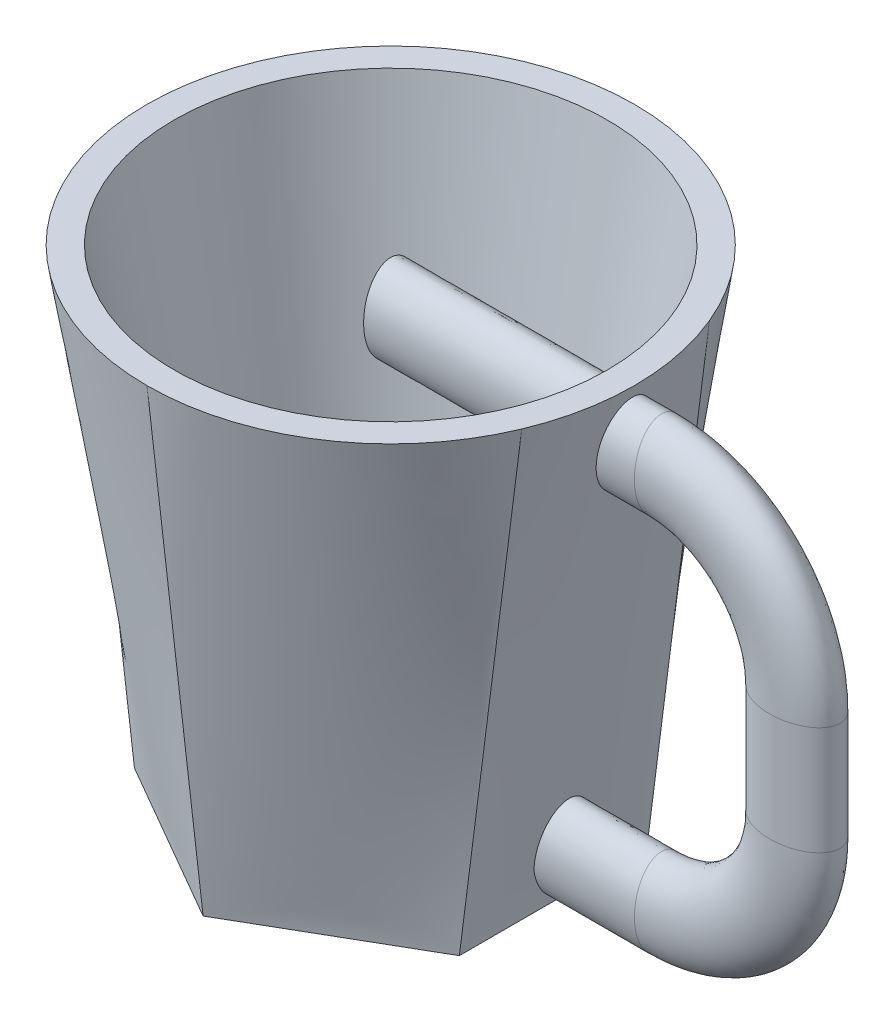
SolidWorks part; units mm, degrees
ref_plane "Front Plane" through (0, 0, 0) normal (0, 0, 1) x (1, 0, 0)
ref_plane "Top Plane" through (0, 0, 0) normal (0, 1, 0) x (1, 0, 0)
ref_plane "Right Plane" through (0, 0, 0) normal (1, 0, 0) x (0, 0, -1)
sketch "Sketch1" plane through (0, 0, 0) normal (0, 1, 0) x (1, 0, 0)
  line L0 (30, 17.3205) -> (0, 34.641)
  line L1 (0, 34.641) -> (-30, 17.3205)
  line L2 (-30, 17.3205) -> (-30, -17.3205)
  line L3 (-30, -17.3205) -> (0, -34.641)
  line L4 (0, -34.641) -> (30, -17.3205)
  line L5 (30, -17.3205) -> (30, 17.3205)
  circle A0 centre (0, 0) radius 30 construction
  dimension "D1" = 60
ref_plane "Plane1" through (0, 90, 0) normal (0, 1, 0) x (1, 0, 0)
sketch "Sketch2" plane through (0, 90, 0) normal (0, 1, 0) x (1, 0, 0)
  arc A0 (-41.5298, 17.3285) -> (-41.5298, -17.3285) centre (0, 0) ccw
  arc A1 (0, 45) -> (-41.5298, 17.3285) centre (0, 0) ccw
  arc A2 (41.5298, 17.3285) -> (0, 45) centre (0, 0) ccw
  arc A3 (41.5298, -17.3285) -> (41.5298, 17.3285) centre (0, 0) ccw
  arc A4 (0, -45) -> (41.5298, -17.3285) centre (0, 0) ccw
  arc A5 (-41.5298, -17.3285) -> (0, -45) centre (0, 0) ccw
  point P3 (0, 0)
  point P10 (0, 0)
  point P14 (-40.3577, 20.6366)
  point P15 (-38.9816, 22.4819)
  point P16 (0, 0)
  point P17 (0, 0)
  point P18 (0, 0)
  point P19 (0, 0)
  point P20 (-41.5298, 17.3205)
  dimension "D1" = 90
loft "Loft4" add profiles "Sketch1", "Sketch2" connector at (-30, 0, -17.3205) connector at (-41.5298, 90, -17.3285)
sketch "Sketch3" plane through (0, 0, 0) normal (0, 0, 1) x (1, 0, 0)
  line L0 (-40, 90) -> (-29.7979, 32.1411)
  line L1 (49.5076, 90) -> (-49.5076, 90) construction
  line L2 (0, 0) -> (0, 90) construction
  line L3 (-30, 0) -> (0, 0) construction
  line L4 (0, 5) -> (0, 109.9812) construction
  line L5 (0, 5) -> (0, 90)
  line L6 (0, 90) -> (-40, 90)
  arc A0 (-29.7979, 32.1411) -> (0, 5) centre (2.6773, 37.8674) ccw
  dimension "D1" = 5
  dimension "D2" = 10
  dimension "D3" = 40
revolve "Cut-Revolve1" cut sketch "Sketch3" angle 360 mid plane about L4
sketch "Sketch4" plane through (0, 0, 0) normal (0, 0, 1) x (1, 0, 0)
  line L0 (0, 80) -> (50, 80)
  line L1 (75, 55) -> (75, 35)
  line L2 (50, 10) -> (31.2811, 10)
  line L3 (30, 0) -> (41.5298, 90) construction
  line L4 (0, 0) -> (30, 0) construction
  line L5 (0, 0) -> (0, 90) construction
  arc A0 (50, 80) -> (75, 55) centre (50, 55) cw
  arc A1 (75, 35) -> (50, 10) centre (50, 35) cw
  point P13 (0, 0)
  point P14 (0, 80)
  point P17 (31.2811, 10)
  point P18 (31.2811, 10)
  point P19 (0, 0)
  dimension "D3" = 25
  dimension "D4" = 25
  dimension "D1" = 70
  dimension "D2" = 10
  dimension "D5" = 105
sketch "Sketch5" plane through (0, 0, 0) normal (1, 0, 0) x (0, 0, -1)
  line L0 (0, 80) -> (0, 55) construction
  ellipse E0 centre (0, 80) end of major axis (0, 88) minor radius 5
  dimension "D1" = 5
  dimension "D2" = 8
sweep "Sweep6" add profiles "Sketch5" path "Sketch4"
